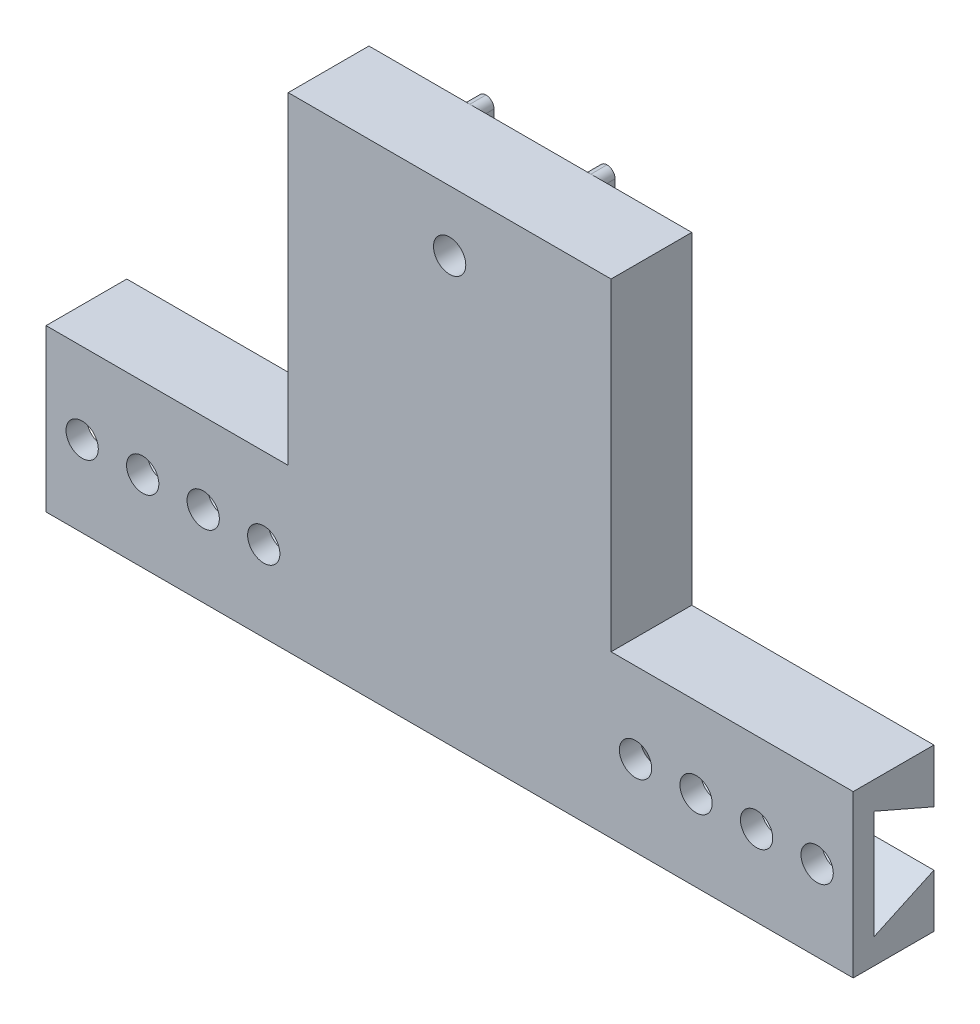
SolidWorks part; units mm, degrees
ref_plane "Front Plane" through (0, 0, 0) normal (0, 0, 1) x (1, 0, 0)
ref_plane "Top Plane" through (0, 0, 0) normal (0, 1, 0) x (1, 0, 0)
ref_plane "Right Plane" through (0, 0, 0) normal (1, 0, 0) x (0, 0, -1)
sketch "Sketch1" plane through (0, 0, 0) normal (0, 1, 0) x (1, 0, 0)
  line L1 (-20, 5) -> (20, 5)
  line L2 (-20, 5) -> (-20, -5)
  line L3 (-20, -5) -> (20, -5)
  line L4 (20, 5) -> (20, -5)
  line L5 (-20, 5) -> (20, -5) construction
  line L6 (-20, -5) -> (20, 5) construction
  point P0 (0, 0)
extrude "Boss-Extrude1" add sketch "Sketch1" against normal blind 60
sketch "Sketch2" plane through (20, 0, 0) normal (1, 0, 0) x (0, 0, -1)
  line L0 (-5, -60) -> (-5, 0) construction
  line L1 (5, -60) -> (-5, -60)
  line L2 (5, -60) -> (5, -40)
  line L3 (5, -40) -> (-5, -40)
  line L4 (-5, -60) -> (-5, -40)
  line L5 (0, -40) -> (0, -60) construction
  line L6 (5, -50) -> (-5, -50) construction
  point P532 (0, -50)
extrude "Boss-Extrude2" add sketch "Sketch2" along normal blind 30 contours L3 L4 L1 L2
sketch "Sketch3" plane through (50, 0, 0) normal (1, 0, 0) x (0, 0, -1)
  line L0 (-2.4245, -50.3998) -> (-2.4245, -56.8645)
  line L1 (-2.4245, -56.8645) -> (5, -53.4322)
  line L2 (5, -60) -> (5, -40) construction
  line L3 (-2.4245, -50.3998) -> (-2.4245, -43.3998)
  line L4 (-2.4245, -43.3998) -> (5, -46.6321)
  line L5 (5, -53.4322) -> (5, -46.6321)
extrude "Cut-Extrude1" cut sketch "Sketch3" against normal blind 30 contours L0 L1 L5 L4 L3
sketch "Sketch6" plane through (0, 0, 5) normal (0, 0, 1) x (1, 0, 0)
  line L0 (50, -40) -> (20, -40) construction
  circle A0 centre (45.5304, -50) radius 2
  dimension "D1" = 10
extrude "Cut-Extrude2" cut sketch "Sketch6" against normal through all contours A0
pattern_linear "LPattern1" count 4 spacing 7.5 along (-1, 0, 0) of "Cut-Extrude2"
mirror "Mirror3" about plane through (0, 0, 0) normal (1, 0, 0) of "LPattern1", "Cut-Extrude1", "Boss-Extrude2"
sketch "Sketch7" plane through (0, 0, 5) normal (0, 0, 1) x (1, 0, 0)
  circle A0 centre (0, -7.5) radius 2
  dimension "D1" = 7.5
extrude "Cut-Extrude3" cut sketch "Sketch7" against normal blind 30
sketch "Sketch8" plane through (0, 0, -5) normal (0, 0, -1) x (-1, 0, 0)
  line L0 (-20, 0) -> (20, 0) construction
  line L1 (-50, -60) -> (50, -60) construction
  line L2 (-8.5, 0) -> (-6.5, 0)
  line L3 (-8.5, 0) -> (-8.5, -60)
  line L4 (-8.5, -60) -> (-6.5, -60)
  line L5 (-6.5, 0) -> (-6.5, -60)
  line L6 (-7.5, -60) -> (-7.5, 0) construction
  line L7 (-8.5, -30) -> (-6.5, -30) construction
  line L9 (-20, -40) -> (-20, 0) construction
  point P662 (-7.5, -30)
  dimension "D1" = 2
  dimension "D2" = 12.5
extrude "Boss-Extrude3" add sketch "Sketch8" along normal blind 2
fillet "Fillet1" radius 1 2 edges at (8.5, 0, -6) (6.5, 0, -6)
mirror "Mirror4" about plane through (0, 0, 0) normal (1, 0, 0) of "Fillet1", "Boss-Extrude3"
